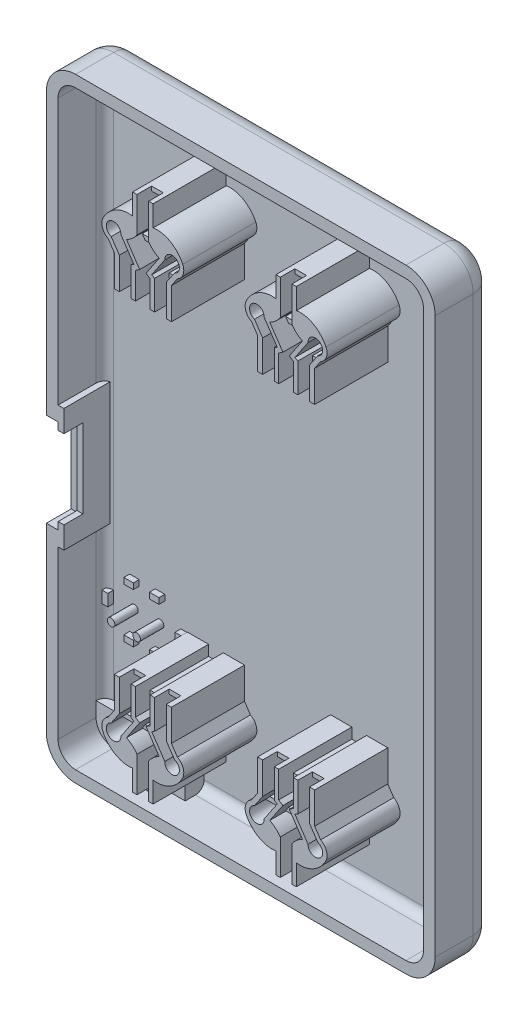
SolidWorks part; units mm, degrees
ref_plane "Alzado" through (0, 0, 0) normal (0, 0, 1) x (1, 0, 0)
ref_plane "Planta" through (0, 0, 0) normal (0, 1, 0) x (1, 0, 0)
ref_plane "Vista lateral" through (0, 0, 0) normal (1, 0, 0) x (0, 0, -1)
sketch "Croquis1" plane through (0, 0, 0) normal (0, 0, 1) x (1, 0, 0)
  line L1 (-97.3166, 96.9231) -> (15.6834, 96.9231)
  line L2 (-107.3166, 86.9231) -> (-107.3166, -103.0769)
  line L3 (-97.3166, -113.0769) -> (15.6834, -113.0769)
  line L4 (25.6834, 86.9231) -> (25.6834, -103.0769)
  arc A0 (15.6834, 96.9231) -> (25.6834, 86.9231) centre (15.6834, 86.9231) cw
  arc A1 (-97.3166, 96.9231) -> (-107.3166, 86.9231) centre (-97.3166, 86.9231) ccw
  arc A2 (15.6834, -113.0769) -> (25.6834, -103.0769) centre (15.6834, -103.0769) ccw
  arc A3 (-107.3166, -103.0769) -> (-97.3166, -113.0769) centre (-97.3166, -103.0769) ccw
  point P6 (25.6834, 96.9231)
  point P9 (-107.3166, 96.9231)
  point P14 (-107.3166, -113.0769)
  dimension "D3" = 10
  dimension "D1" = 210
  dimension "D2" = 133
extrude "Saliente-Extruir1" add sketch "Croquis1" along normal blind 20
fillet "Redondeo1" radius 7 8 edges at (-40.8166, 96.9231, 0) (22.7544, 93.9941, 0) (25.6834, -8.0769, 0) (22.7544, -110.148, 0) (-40.8166, -113.0769, 0) (-104.3877, -110.148, 0) (-107.3166, -8.0769, 0) (-104.3877, 93.9941, 0)
shell "Vaciado1" thickness 4 removed face at (-40.8166, -8.0769, 20)
sketch "Croquis4" plane through (0, 0, 0) normal (0, 0, 1) x (1, 0, 0)
  line L11 (-95.8166, 81.9231) -> (-103.3166, 81.9231)
  line L12 (-97.3166, -109.0769) -> (15.6834, -109.0769) construction
  line L17 (-103.3166, 86.9231) -> (-103.3166, -103.0769) construction
  line L19 (-85.549, -109.0769) -> (-78.3884, -109.0769)
  line L23 (-92.3166, 85.4231) -> (-92.3166, 92.9231)
  line L40 (15.6834, 92.9231) -> (-97.3166, 92.9231) construction
  line L41 (-40.8166, 96.9231) -> (-40.8166, -113.0769)
  line L42 (-85.549, -109.0769) -> (-85.549, -113.0769)
  line L43 (-107.3166, -8.0769) -> (25.6834, -8.0769)
  line L44 (-85.549, -113.0769) -> (-78.3884, -113.0769)
  line L45 (-78.3884, -109.0769) -> (-78.3884, -113.0769)
  line L47 (14.1834, 81.9231) -> (21.6834, 81.9231)
  line L48 (25.6834, -113.0769) -> (-107.3166, -113.0769)
  line L50 (25.6834, -113.0769) -> (25.6834, 96.9231)
  line L51 (25.6834, 96.9231) -> (-107.3166, 96.9231)
  line L52 (-107.3166, -113.0769) -> (-107.3166, 96.9231)
  line L53 (10.6834, 85.4231) -> (10.6834, 92.9231)
  line L54 (-92.3166, -101.5769) -> (-92.3166, -109.0769)
  line L55 (-95.8166, -98.0769) -> (-103.3166, -98.0769)
  line L56 (10.6834, -101.5769) -> (10.6834, -109.0769)
  line L57 (14.1834, -98.0769) -> (21.6834, -98.0769)
  circle A6 centre (-95.8166, 85.4231) radius 3.5
  circle A12 centre (-95.8166, 85.4231) radius 1.6
  circle A14 centre (14.1834, 85.4231) radius 1.6
  circle A15 centre (14.1834, 85.4231) radius 3.5
  circle A17 centre (-95.8166, -101.5769) radius 1.6
  circle A18 centre (-95.8166, -101.5769) radius 3.5
  circle A19 centre (14.1834, -101.5769) radius 1.6
  circle A20 centre (14.1834, -101.5769) radius 3.5
  arc A21 (-103.3166, 81.9231) -> (-92.3166, 92.9231) centre (-95.8166, 85.4231) cw
  arc A22 (10.6834, 92.9231) -> (21.6834, 81.9231) centre (14.1834, 85.4231) cw
  arc A23 (21.6834, -98.0769) -> (10.6834, -109.0769) centre (14.1834, -101.5769) cw
  arc A24 (-103.3166, -98.0769) -> (-92.3166, -109.0769) centre (-95.8166, -101.5769) ccw
extrude "Cortar-Extruir5" cut sketch "Croquis4" along normal through all both and the other way through all from surface contours A17 | A19 | A14 | A12 region at (-95.8166, 85.4231, 0) region at (14.1834, 85.4231, 0) region at (-95.8166, -101.5769, 0) region at (14.1834, -101.5769, 0) starting at face at (-40.8166, -8.0769, 4)
sketch "Croquis5" plane through (0, 0, 0) normal (0, 0, 1) x (1, 0, 0)
  line L8 (-144.4431, 85.9333) -> (-144.4431, 50.2681) construction
  line L150 (-75.9086, 63.6344) -> (-71.0838, 63.6344)
  line L167 (-146.4431, 85.9333) -> (-146.4431, 73.9331)
  line L178 (-146.4431, 73.9331) -> (-142.4431, 73.9331)
  line L185 (-146.4431, 73.9331) -> (-146.4431, 85.9333)
  line L187 (-146.4431, 85.9333) -> (-142.4431, 85.9333)
  line L190 (-146.4431, 85.9333) -> (-147.9431, 85.9333)
  line L196 (-142.4431, 73.9331) -> (-142.4431, 85.9333)
  line L197 (-147.4727, 64.6757) -> (-148.4665, 64.1128)
  line L202 (-152.4665, 64.926) -> (-152.4665, 54.1125)
  line L203 (-148.4665, 54.1125) -> (-152.4665, 54.1125)
  line L204 (-154.2167, 64.8384) -> (-156.2619, 67.8705)
  line L212 (-148.4665, 64.1128) -> (-148.4665, 54.1125)
  line L213 (-151.9463, 71.308) -> (-147.4727, 64.6757)
  line L215 (-152.4665, 54.1125) -> (-154.2167, 54.1125)
  line L216 (-152.4665, 64.926) -> (-155.2624, 69.0712)
  line L217 (-154.2167, 54.1125) -> (-154.2167, 64.8384)
  line L218 (-142.4431, 85.9333) -> (-142.4431, 73.9331)
  line L219 (-145.5428, 64.1681) -> (-146.9665, 63.2078)
  line L221 (-146.9665, 63.2078) -> (-146.9665, 54.1125)
  line L223 (-148.4665, 54.1125) -> (-146.9665, 54.1125)
  line L224 (-150.0254, 70.8139) -> (-145.5428, 64.1681)
  line L225 (-147.9431, 85.9333) -> (-147.9431, 78.778)
  line L226 (-140.4198, 54.1125) -> (-141.9198, 54.1125)
  line L227 (-141.9198, 63.2078) -> (-141.9198, 54.1125)
  line L228 (-143.3435, 64.1681) -> (-141.9198, 63.2078)
  line L229 (-138.8608, 70.8139) -> (-143.3435, 64.1681)
  line L230 (-142.4431, 85.9333) -> (-140.9431, 85.9333)
  line L231 (-140.9431, 85.9333) -> (-140.9431, 78.778)
  line L232 (-134.6696, 64.8384) -> (-132.6244, 67.8705)
  line L233 (-134.6696, 54.1125) -> (-134.6696, 64.8384)
  line L234 (-136.4198, 54.1125) -> (-134.6696, 54.1125)
  line L235 (-136.4198, 64.926) -> (-136.4198, 54.1125)
  line L236 (-136.4198, 64.926) -> (-133.6238, 69.0712)
  line L237 (-136.94, 71.308) -> (-141.4135, 64.6757)
  line L238 (-141.4135, 64.6757) -> (-140.4198, 64.1128)
  line L239 (-140.4198, 64.1128) -> (-140.4198, 54.1125)
  line L241 (-107.3166, 96.9231) -> (-100.3166, 96.9231)
  line L242 (-107.3166, 96.9231) -> (-107.3166, 86.9231)
  line L253 (25.6834, -113.0769) -> (-107.3166, -113.0769)
  line L254 (25.6834, -113.0769) -> (25.6834, 96.9231)
  line L255 (25.6834, 96.9231) -> (-107.3166, 96.9231)
  line L257 (-107.3166, -113.0769) -> (-107.3166, 96.9231)
  line L269 (-18.84, -74.2618) -> (-18.84, -65.1665)
  line L283 (-97.3166, 89.9231) -> (-100.3166, 89.9231)
  line L286 (-100.3166, 89.9231) -> (18.6834, 89.9231)
  line L287 (-100.3166, 89.9231) -> (-100.3166, 39.9231)
  line L288 (-100.3166, 39.9231) -> (18.6834, 39.9231)
  line L289 (18.6834, 89.9231) -> (18.6834, 39.9231)
  line L290 (18.6834, 86.9231) -> (18.6834, -103.0769) construction
  line L292 (-100.3166, 89.9231) -> (-80.3166, 89.9231)
  line L293 (-100.3166, 89.9231) -> (-100.3166, 39.9231)
  line L294 (-100.3166, 39.9231) -> (-80.3166, 39.9231)
  line L295 (-80.3166, 89.9231) -> (-80.3166, 39.9231)
  line L297 (18.6834, 39.9231) -> (-1.3166, 39.9231)
  line L298 (18.6834, 39.9231) -> (18.6834, 89.9231)
  line L299 (18.6834, 89.9231) -> (-1.3166, 89.9231)
  line L300 (-1.3166, 39.9231) -> (-1.3166, 89.9231)
  line L302 (-80.3166, 39.9231) -> (-50.3166, 39.9231)
  line L303 (-80.3166, 39.9231) -> (-80.3166, 89.9231)
  line L304 (-80.3166, 89.9231) -> (-50.3166, 89.9231)
  line L305 (-50.3166, 39.9231) -> (-50.3166, 89.9231)
  line L307 (-1.3166, 39.9231) -> (-31.3166, 39.9231)
  line L308 (-1.3166, 39.9231) -> (-1.3166, 89.9231)
  line L309 (-1.3166, 89.9231) -> (-31.3166, 89.9231)
  line L310 (-31.3166, 39.9231) -> (-31.3166, 89.9231)
  line L313 (-130.4431, 54.1125) -> (-158.4431, 85.9333)
  line L317 (-67.3166, 68.8333) -> (-67.3166, 80.8335)
  line L318 (-72.8198, 66.2081) -> (-68.3462, 59.5758)
  line L319 (-63.3166, 80.8335) -> (-61.8166, 80.8335)
  line L320 (-61.2933, 59.013) -> (-61.2933, 49.0127)
  line L321 (-63.3166, 80.8335) -> (-63.3166, 68.8333)
  line L322 (-70.8989, 65.714) -> (-66.4163, 59.0683)
  line L323 (-59.7343, 65.714) -> (-64.217, 59.0683)
  line L324 (-57.2933, 59.8262) -> (-54.4974, 63.9714)
  line L325 (-75.0902, 59.7386) -> (-77.1354, 62.7707)
  line L326 (-75.0902, 49.0127) -> (-75.0902, 59.7386)
  line L327 (-67.3166, 80.8335) -> (-67.3166, 68.8333)
  line L329 (-61.8166, 80.8335) -> (-61.8166, 73.6781)
  line L330 (-68.3462, 59.5758) -> (-69.34, 59.013)
  line L331 (-66.4163, 59.0683) -> (-67.84, 58.108)
  line L333 (-68.8166, 80.8335) -> (-68.8166, 73.6781)
  line L334 (-55.5431, 49.0127) -> (-55.5431, 59.7386)
  line L335 (-73.34, 49.0127) -> (-75.0902, 49.0127)
  line L336 (-55.5431, 59.7386) -> (-53.4979, 62.7707)
  line L337 (-57.2933, 59.8262) -> (-57.2933, 49.0127)
  line L338 (-67.84, 58.108) -> (-67.84, 49.0127)
  line L339 (-69.34, 49.0127) -> (-67.84, 49.0127)
  line L340 (-57.8135, 66.2081) -> (-62.287, 59.5758)
  line L341 (-63.3166, 68.8333) -> (-63.3166, 80.8335)
  line L342 (-73.34, 59.8262) -> (-73.34, 49.0127)
  line L343 (-61.2933, 49.0127) -> (-62.7933, 49.0127)
  line L345 (-64.217, 59.0683) -> (-62.7933, 58.108)
  line L346 (-62.287, 59.5758) -> (-61.2933, 59.013)
  line L347 (-73.34, 59.8262) -> (-76.1359, 63.9714)
  line L348 (-57.2933, 49.0127) -> (-55.5431, 49.0127)
  line L350 (-62.7933, 58.108) -> (-62.7933, 49.0127)
  line L352 (-67.3166, 80.8335) -> (-68.8166, 80.8335)
  line L353 (-69.34, 59.013) -> (-69.34, 49.0127)
  line L392 (-24.34, -65.1665) -> (-26.0902, -65.1665)
  line L393 (-14.3166, -96.9873) -> (-12.8166, -96.9873)
  line L394 (-20.34, -65.1665) -> (-18.84, -65.1665)
  line L395 (-19.8166, -96.9873) -> (-19.8166, -89.832)
  line L396 (-26.0902, -65.1665) -> (-26.0902, -75.8924)
  line L397 (-13.287, -75.7297) -> (-12.2933, -75.1668)
  line L398 (-13.7933, -74.2618) -> (-13.7933, -65.1665)
  line L399 (-26.0902, -75.8924) -> (-28.1354, -78.9245)
  line L400 (-12.8166, -96.9873) -> (-12.8166, -89.832)
  line L401 (-6.5431, -75.8924) -> (-4.4979, -78.9245)
  line L402 (-12.2933, -65.1665) -> (-13.7933, -65.1665)
  line L403 (-20.34, -75.1668) -> (-20.34, -65.1665)
  line L404 (-21.8989, -81.8679) -> (-17.4163, -75.2221)
  line L405 (-10.7343, -81.8679) -> (-15.217, -75.2221)
  line L406 (-24.34, -75.98) -> (-27.1359, -80.1252)
  line L407 (-15.217, -75.2221) -> (-13.7933, -74.2618)
  line L408 (-17.4163, -75.2221) -> (-18.84, -74.2618)
  line L409 (-19.3462, -75.7297) -> (-20.34, -75.1668)
  line L410 (-8.2933, -75.98) -> (-8.2933, -65.1665)
  line L411 (-14.3166, -96.9873) -> (-14.3166, -84.9871)
  line L412 (-14.3166, -84.9871) -> (-14.3166, -96.9873)
  line L413 (-24.34, -75.98) -> (-24.34, -65.1665)
  line L414 (-12.2933, -75.1668) -> (-12.2933, -65.1665)
  line L415 (-8.2933, -65.1665) -> (-6.5431, -65.1665)
  line L416 (-8.8135, -82.362) -> (-13.287, -75.7297)
  line L417 (-18.3166, -96.9873) -> (-18.3166, -84.9871)
  line L418 (-6.5431, -65.1665) -> (-6.5431, -75.8924)
  line L419 (-23.8198, -82.362) -> (-19.3462, -75.7297)
  line L420 (-8.2933, -75.98) -> (-5.4974, -80.1252)
  line L421 (-18.3166, -96.9873) -> (-19.8166, -96.9873)
  line L422 (-18.3166, -84.9871) -> (-18.3166, -96.9873)
  line L423 (-69.34, -75.1668) -> (-69.34, -65.1665)
  line L424 (-67.3166, -96.9873) -> (-68.8166, -96.9873)
  line L425 (-62.7933, -74.2618) -> (-62.7933, -65.1665)
  line L426 (-57.2933, -65.1665) -> (-55.5431, -65.1665)
  line L427 (-73.34, -75.98) -> (-76.1359, -80.1252)
  line L428 (-62.287, -75.7297) -> (-61.2933, -75.1668)
  line L429 (-64.217, -75.2221) -> (-62.7933, -74.2618)
  line L430 (-61.2933, -65.1665) -> (-62.7933, -65.1665)
  line L431 (-73.34, -75.98) -> (-73.34, -65.1665)
  line L432 (-63.3166, -84.9871) -> (-63.3166, -96.9873)
  line L433 (-57.8135, -82.362) -> (-62.287, -75.7297)
  line L434 (-69.34, -65.1665) -> (-67.84, -65.1665)
  line L435 (-67.84, -74.2618) -> (-67.84, -65.1665)
  line L436 (-57.2933, -75.98) -> (-57.2933, -65.1665)
  line L437 (-55.5431, -75.8924) -> (-53.4979, -78.9245)
  line L438 (-73.34, -65.1665) -> (-75.0902, -65.1665)
  line L439 (-55.5431, -65.1665) -> (-55.5431, -75.8924)
  line L440 (-68.8166, -96.9873) -> (-68.8166, -89.832)
  line L441 (-66.4163, -75.2221) -> (-67.84, -74.2618)
  line L442 (-68.3462, -75.7297) -> (-69.34, -75.1668)
  line L443 (-61.8166, -96.9873) -> (-61.8166, -89.832)
  line L444 (-67.3166, -96.9873) -> (-67.3166, -84.9871)
  line L445 (-75.0902, -65.1665) -> (-75.0902, -75.8924)
  line L446 (-75.0902, -75.8924) -> (-77.1354, -78.9245)
  line L447 (-57.2933, -75.98) -> (-54.4974, -80.1252)
  line L448 (-59.7343, -81.8679) -> (-64.217, -75.2221)
  line L449 (-70.8989, -81.8679) -> (-66.4163, -75.2221)
  line L450 (-63.3166, -96.9873) -> (-63.3166, -84.9871)
  line L451 (-61.2933, -75.1668) -> (-61.2933, -65.1665)
  line L452 (-63.3166, -96.9873) -> (-61.8166, -96.9873)
  line L453 (-72.8198, -82.362) -> (-68.3462, -75.7297)
  line L454 (-67.3166, -84.9871) -> (-67.3166, -96.9873)
  line L457 (-73.34, 49.0127) -> (-69.34, 49.0127)
  line L458 (-73.34, 49.0127) -> (-73.34, 50.515)
  line L459 (-73.34, 50.515) -> (-69.34, 50.515)
  line L460 (-69.34, 49.0127) -> (-69.34, 50.515)
  line L461 (-61.2933, 49.0127) -> (-57.2933, 49.0127)
  line L462 (-61.2933, 49.0127) -> (-61.2933, 50.515)
  line L463 (-61.2933, 50.515) -> (-57.2933, 50.515)
  line L464 (-57.2933, 49.0127) -> (-57.2933, 50.515)
  line L465 (-61.2933, 58.108) -> (-57.2933, 58.108)
  line L466 (-61.2933, 58.108) -> (-61.2933, 56.6032)
  line L467 (-61.2933, 56.6032) -> (-57.2933, 56.6032)
  line L468 (-57.2933, 58.108) -> (-57.2933, 56.6032)
  line L469 (-69.34, 56.6032) -> (-73.34, 56.6032)
  line L470 (-69.34, 56.6032) -> (-69.34, 58.108)
  line L471 (-69.34, 58.108) -> (-73.34, 58.108)
  line L472 (-73.34, 56.6032) -> (-73.34, 58.108)
  line L476 (-71.0838, 63.6344) -> (-72.0951, 65.1338)
  line L477 (-72.0951, 65.1338) -> (-77.5101, 65.1338)
  line L478 (-70.5075, 65.1338) -> (-60.1257, 65.1338)
  line L480 (-58.5382, 65.1338) -> (-53.1232, 65.1338)
  line L482 (-69.4962, 63.6344) -> (-61.1371, 63.6344)
  line L484 (-59.5495, 63.6344) -> (-54.7246, 63.6344)
  line L487 (-67.3166, 80.8335) -> (-63.3166, 80.8335)
  line L488 (-67.3166, 80.8335) -> (-67.3166, 79.3376)
  line L489 (-67.3166, 79.3376) -> (-63.3166, 79.3376)
  line L490 (-63.3166, 80.8335) -> (-63.3166, 79.3376)
  line L495 (-67.84, 54.1125) -> (-62.7933, 54.1125)
  line L496 (-67.84, 54.1125) -> (-67.84, 52.6136)
  line L497 (-67.84, 52.6136) -> (-62.7933, 52.6136)
  line L498 (-62.7933, 54.1125) -> (-62.7933, 52.6136)
  line L499 (-18.84, 54.1125) -> (-18.84, 52.6136)
  line L500 (-13.7933, 52.6136) -> (-18.84, 52.6136)
  line L501 (-13.7933, 54.1125) -> (-13.7933, 52.6136)
  line L502 (-13.7933, 54.1125) -> (-18.84, 54.1125)
  line L503 (-18.3166, 80.8335) -> (-18.3166, 79.3376)
  line L504 (-14.3166, 79.3376) -> (-18.3166, 79.3376)
  line L505 (-14.3166, 80.8335) -> (-14.3166, 79.3376)
  line L506 (-14.3166, 80.8335) -> (-18.3166, 80.8335)
  line L507 (-22.0838, 63.6344) -> (-26.9086, 63.6344)
  line L508 (-12.1371, 63.6344) -> (-20.4962, 63.6344)
  line L509 (-23.0951, 65.1338) -> (-28.5101, 65.1338)
  line L510 (-11.1257, 65.1338) -> (-21.5075, 65.1338)
  line L511 (-9.5382, 65.1338) -> (-4.1232, 65.1338)
  line L512 (-10.5495, 63.6344) -> (-9.5382, 65.1338)
  line L513 (-8.2933, 56.6032) -> (-8.2933, 58.108)
  line L514 (-12.2933, 58.108) -> (-8.2933, 58.108)
  line L515 (-12.2933, 56.6032) -> (-12.2933, 58.108)
  line L516 (-12.2933, 56.6032) -> (-8.2933, 56.6032)
  line L517 (-24.34, 58.108) -> (-24.34, 56.6032)
  line L518 (-20.34, 56.6032) -> (-24.34, 56.6032)
  line L519 (-20.34, 58.108) -> (-20.34, 56.6032)
  line L520 (-20.34, 58.108) -> (-24.34, 58.108)
  line L521 (-24.34, 49.0127) -> (-24.34, 50.515)
  line L522 (-20.34, 50.515) -> (-24.34, 50.515)
  line L523 (-20.34, 49.0127) -> (-20.34, 50.515)
  line L524 (-20.34, 49.0127) -> (-24.34, 49.0127)
  line L525 (-12.2933, 49.0127) -> (-12.2933, 50.515)
  line L526 (-8.2933, 50.515) -> (-12.2933, 50.515)
  line L527 (-8.2933, 49.0127) -> (-8.2933, 50.515)
  line L528 (-8.2933, 49.0127) -> (-12.2933, 49.0127)
  line L529 (-12.2933, 59.013) -> (-12.2933, 49.0127)
  line L530 (-14.3166, 80.8335) -> (-12.8166, 80.8335)
  line L531 (-18.84, 58.108) -> (-18.84, 49.0127)
  line L532 (-24.34, 49.0127) -> (-26.0902, 49.0127)
  line L533 (-8.2933, 59.8262) -> (-5.4974, 63.9714)
  line L534 (-19.3462, 59.5758) -> (-20.34, 59.013)
  line L535 (-17.4163, 59.0683) -> (-18.84, 58.108)
  line L536 (-20.34, 49.0127) -> (-18.84, 49.0127)
  line L537 (-8.2933, 59.8262) -> (-8.2933, 49.0127)
  line L538 (-18.3166, 68.8333) -> (-18.3166, 80.8335)
  line L539 (-23.8198, 66.2081) -> (-19.3462, 59.5758)
  line L540 (-12.2933, 49.0127) -> (-13.7933, 49.0127)
  line L541 (-13.7933, 58.108) -> (-13.7933, 49.0127)
  line L542 (-24.34, 59.8262) -> (-24.34, 49.0127)
  line L543 (-26.0902, 59.7386) -> (-28.1354, 62.7707)
  line L544 (-8.2933, 49.0127) -> (-6.5431, 49.0127)
  line L545 (-26.0902, 49.0127) -> (-26.0902, 59.7386)
  line L546 (-12.8166, 80.8335) -> (-12.8166, 73.6781)
  line L547 (-15.217, 59.0683) -> (-13.7933, 58.108)
  line L548 (-13.287, 59.5758) -> (-12.2933, 59.013)
  line L549 (-19.8166, 80.8335) -> (-19.8166, 73.6781)
  line L550 (-14.3166, 80.8335) -> (-14.3166, 68.8333)
  line L551 (-6.5431, 49.0127) -> (-6.5431, 59.7386)
  line L552 (-6.5431, 59.7386) -> (-4.4979, 62.7707)
  line L553 (-24.34, 59.8262) -> (-27.1359, 63.9714)
  line L554 (-21.8989, 65.714) -> (-17.4163, 59.0683)
  line L555 (-10.7343, 65.714) -> (-15.217, 59.0683)
  line L556 (-18.3166, 80.8335) -> (-18.3166, 68.8333)
  line L557 (-20.34, 59.013) -> (-20.34, 49.0127)
  line L558 (-18.3166, 80.8335) -> (-19.8166, 80.8335)
  line L559 (-8.8135, 66.2081) -> (-13.287, 59.5758)
  line L560 (-14.3166, 68.8333) -> (-14.3166, 80.8335)
  line L561 (-5.7246, 63.6344) -> (-10.5495, 63.6344)
  line L562 (-100.3166, -8.0769) -> (18.6834, -8.0769)
  line L563 (-100.3166, -103.0769) -> (-100.3166, 86.9231) construction
  line L564 (-5.7246, -79.7882) -> (-10.5495, -79.7882)
  line L565 (-14.3166, -84.9871) -> (-14.3166, -96.9873)
  line L566 (-8.8135, -82.362) -> (-13.287, -75.7297)
  line L567 (-18.3166, -96.9873) -> (-19.8166, -96.9873)
  line L568 (-20.34, -75.1668) -> (-20.34, -65.1665)
  line L569 (-18.3166, -96.9873) -> (-18.3166, -84.9871)
  line L570 (-10.7343, -81.8679) -> (-15.217, -75.2221)
  line L571 (-21.8989, -81.8679) -> (-17.4163, -75.2221)
  line L572 (-24.34, -75.98) -> (-27.1359, -80.1252)
  line L573 (-6.5431, -75.8924) -> (-4.4979, -78.9245)
  line L574 (-6.5431, -65.1665) -> (-6.5431, -75.8924)
  line L575 (-14.3166, -96.9873) -> (-14.3166, -84.9871)
  line L576 (-19.8166, -96.9873) -> (-19.8166, -89.832)
  line L577 (-13.287, -75.7297) -> (-12.2933, -75.1668)
  line L578 (-15.217, -75.2221) -> (-13.7933, -74.2618)
  line L579 (-12.8166, -96.9873) -> (-12.8166, -89.832)
  line L580 (-26.0902, -65.1665) -> (-26.0902, -75.8924)
  line L581 (-8.2933, -65.1665) -> (-6.5431, -65.1665)
  line L582 (-26.0902, -75.8924) -> (-28.1354, -78.9245)
  line L583 (-24.34, -75.98) -> (-24.34, -65.1665)
  line L584 (-13.7933, -74.2618) -> (-13.7933, -65.1665)
  line L585 (-12.2933, -65.1665) -> (-13.7933, -65.1665)
  line L586 (-23.8198, -82.362) -> (-19.3462, -75.7297)
  line L587 (-18.3166, -84.9871) -> (-18.3166, -96.9873)
  line L588 (-8.2933, -75.98) -> (-8.2933, -65.1665)
  line L589 (-20.34, -65.1665) -> (-18.84, -65.1665)
  line L590 (-17.4163, -75.2221) -> (-18.84, -74.2618)
  line L591 (-19.3462, -75.7297) -> (-20.34, -75.1668)
  line L592 (-8.2933, -75.98) -> (-5.4974, -80.1252)
  line L593 (-24.34, -65.1665) -> (-26.0902, -65.1665)
  line L594 (-18.84, -74.2618) -> (-18.84, -65.1665)
  line L595 (-14.3166, -96.9873) -> (-12.8166, -96.9873)
  line L596 (-12.2933, -75.1668) -> (-12.2933, -65.1665)
  line L597 (-8.2933, -65.1665) -> (-12.2933, -65.1665)
  line L598 (-8.2933, -65.1665) -> (-8.2933, -66.6689)
  line L599 (-8.2933, -66.6689) -> (-12.2933, -66.6689)
  line L600 (-12.2933, -65.1665) -> (-12.2933, -66.6689)
  line L601 (-20.34, -65.1665) -> (-24.34, -65.1665)
  line L602 (-20.34, -65.1665) -> (-20.34, -66.6689)
  line L603 (-20.34, -66.6689) -> (-24.34, -66.6689)
  line L604 (-24.34, -65.1665) -> (-24.34, -66.6689)
  line L605 (-20.34, -74.2618) -> (-24.34, -74.2618)
  line L606 (-20.34, -74.2618) -> (-20.34, -72.757)
  line L607 (-20.34, -72.757) -> (-24.34, -72.757)
  line L608 (-24.34, -74.2618) -> (-24.34, -72.757)
  line L609 (-12.2933, -72.757) -> (-8.2933, -72.757)
  line L610 (-12.2933, -72.757) -> (-12.2933, -74.2618)
  line L611 (-12.2933, -74.2618) -> (-8.2933, -74.2618)
  line L612 (-8.2933, -72.757) -> (-8.2933, -74.2618)
  line L613 (-10.5495, -79.7882) -> (-9.5382, -81.2876)
  line L614 (-9.5382, -81.2876) -> (-4.1232, -81.2876)
  line L615 (-11.1257, -81.2876) -> (-21.5075, -81.2876)
  line L616 (-23.0951, -81.2876) -> (-28.5101, -81.2876)
  line L617 (-12.1371, -79.7882) -> (-20.4962, -79.7882)
  line L618 (-22.0838, -79.7882) -> (-26.9086, -79.7882)
  line L619 (-14.3166, -96.9873) -> (-18.3166, -96.9873)
  line L620 (-14.3166, -96.9873) -> (-14.3166, -95.4915)
  line L621 (-14.3166, -95.4915) -> (-18.3166, -95.4915)
  line L622 (-18.3166, -96.9873) -> (-18.3166, -95.4915)
  line L623 (-13.7933, -70.2663) -> (-18.84, -70.2663)
  line L624 (-13.7933, -70.2663) -> (-13.7933, -68.7675)
  line L625 (-13.7933, -68.7675) -> (-18.84, -68.7675)
  line L626 (-18.84, -70.2663) -> (-18.84, -68.7675)
  line L627 (-62.7933, -70.2663) -> (-62.7933, -68.7675)
  line L628 (-67.84, -68.7675) -> (-62.7933, -68.7675)
  line L629 (-67.84, -70.2663) -> (-67.84, -68.7675)
  line L630 (-67.84, -70.2663) -> (-62.7933, -70.2663)
  line L631 (-63.3166, -96.9873) -> (-63.3166, -95.4915)
  line L632 (-67.3166, -95.4915) -> (-63.3166, -95.4915)
  line L633 (-67.3166, -96.9873) -> (-67.3166, -95.4915)
  line L634 (-67.3166, -96.9873) -> (-63.3166, -96.9873)
  line L635 (-59.5495, -79.7882) -> (-54.7246, -79.7882)
  line L636 (-69.4962, -79.7882) -> (-61.1371, -79.7882)
  line L637 (-58.5382, -81.2876) -> (-53.1232, -81.2876)
  line L638 (-70.5075, -81.2876) -> (-60.1257, -81.2876)
  line L639 (-72.0951, -81.2876) -> (-77.5101, -81.2876)
  line L640 (-71.0838, -79.7882) -> (-72.0951, -81.2876)
  line L641 (-73.34, -72.757) -> (-73.34, -74.2618)
  line L642 (-69.34, -74.2618) -> (-73.34, -74.2618)
  line L643 (-69.34, -72.757) -> (-69.34, -74.2618)
  line L644 (-69.34, -72.757) -> (-73.34, -72.757)
  line L645 (-57.2933, -74.2618) -> (-57.2933, -72.757)
  line L646 (-61.2933, -72.757) -> (-57.2933, -72.757)
  line L647 (-61.2933, -74.2618) -> (-61.2933, -72.757)
  line L648 (-61.2933, -74.2618) -> (-57.2933, -74.2618)
  line L649 (-57.2933, -65.1665) -> (-57.2933, -66.6689)
  line L650 (-61.2933, -66.6689) -> (-57.2933, -66.6689)
  line L651 (-61.2933, -65.1665) -> (-61.2933, -66.6689)
  line L652 (-61.2933, -65.1665) -> (-57.2933, -65.1665)
  line L653 (-69.34, -65.1665) -> (-69.34, -66.6689)
  line L654 (-73.34, -66.6689) -> (-69.34, -66.6689)
  line L655 (-73.34, -65.1665) -> (-73.34, -66.6689)
  line L656 (-73.34, -65.1665) -> (-69.34, -65.1665)
  line L657 (-69.34, -75.1668) -> (-69.34, -65.1665)
  line L658 (-67.3166, -96.9873) -> (-68.8166, -96.9873)
  line L659 (-62.7933, -74.2618) -> (-62.7933, -65.1665)
  line L660 (-57.2933, -65.1665) -> (-55.5431, -65.1665)
  line L661 (-73.34, -75.98) -> (-76.1359, -80.1252)
  line L662 (-62.287, -75.7297) -> (-61.2933, -75.1668)
  line L663 (-64.217, -75.2221) -> (-62.7933, -74.2618)
  line L664 (-61.2933, -65.1665) -> (-62.7933, -65.1665)
  line L665 (-73.34, -75.98) -> (-73.34, -65.1665)
  line L666 (-63.3166, -84.9871) -> (-63.3166, -96.9873)
  line L667 (-57.8135, -82.362) -> (-62.287, -75.7297)
  line L668 (-69.34, -65.1665) -> (-67.84, -65.1665)
  line L669 (-67.84, -74.2618) -> (-67.84, -65.1665)
  line L670 (-57.2933, -75.98) -> (-57.2933, -65.1665)
  line L671 (-55.5431, -75.8924) -> (-53.4979, -78.9245)
  line L672 (-73.34, -65.1665) -> (-75.0902, -65.1665)
  line L673 (-55.5431, -65.1665) -> (-55.5431, -75.8924)
  line L674 (-68.8166, -96.9873) -> (-68.8166, -89.832)
  line L675 (-66.4163, -75.2221) -> (-67.84, -74.2618)
  line L676 (-68.3462, -75.7297) -> (-69.34, -75.1668)
  line L677 (-61.8166, -96.9873) -> (-61.8166, -89.832)
  line L678 (-67.3166, -96.9873) -> (-67.3166, -84.9871)
  line L679 (-75.0902, -65.1665) -> (-75.0902, -75.8924)
  line L680 (-75.0902, -75.8924) -> (-77.1354, -78.9245)
  line L681 (-57.2933, -75.98) -> (-54.4974, -80.1252)
  line L682 (-59.7343, -81.8679) -> (-64.217, -75.2221)
  line L683 (-70.8989, -81.8679) -> (-66.4163, -75.2221)
  line L684 (-63.3166, -96.9873) -> (-63.3166, -84.9871)
  line L685 (-61.2933, -75.1668) -> (-61.2933, -65.1665)
  line L686 (-63.3166, -96.9873) -> (-61.8166, -96.9873)
  line L687 (-72.8198, -82.362) -> (-68.3462, -75.7297)
  line L688 (-67.3166, -84.9871) -> (-67.3166, -96.9873)
  line L689 (-75.9086, -79.7882) -> (-71.0838, -79.7882)
  line L690 (-97.3166, -109.0769) -> (15.6834, -109.0769) construction
  line L691 (-81.8788, -113.0769) -> (-74.9415, -113.0769)
  line L692 (-81.8788, -113.0769) -> (-81.8788, -109.0769)
  line L693 (-81.8788, -109.0769) -> (-74.9415, -109.0769)
  line L694 (-74.9415, -113.0769) -> (-74.9415, -109.0769)
  line L695 (-87.3438, -109.0769) -> (-81.8788, -109.0769)
  line L697 (-84.8438, -103.0769) -> (-71.844, -103.0769)
  line L698 (-87.3438, -103.0769) -> (-87.3438, -109.0769)
  line L699 (-84.8438, -100.5769) -> (-71.844, -100.5769)
  line L700 (-69.344, -103.0769) -> (-69.344, -109.0769)
  line L701 (-97.3166, -109.0769) -> (15.6834, -109.0769) construction
  line L702 (-74.9415, -109.0769) -> (-69.344, -109.0769)
  line L704 (-78.4102, -109.0769) -> (-78.4102, -113.0769)
  line L705 (-100.3166, -74.8411) -> (-77.3166, -74.8411)
  line L706 (-100.3166, -74.8411) -> (-100.3166, -59.8411)
  line L707 (-100.3166, -59.8411) -> (-77.3166, -59.8411)
  line L708 (-77.3166, -74.8411) -> (-77.3166, -59.8411)
  line L709 (-77.3166, -74.8411) -> (-82.8166, -74.8411)
  line L710 (-77.3166, -74.8411) -> (-77.3166, -59.8411)
  line L711 (-77.3166, -59.8411) -> (-82.8166, -59.8411)
  line L713 (-94.8166, -59.8411) -> (-91.5666, -59.8411)
  line L714 (-91.5666, -59.8411) -> (-86.0666, -59.8411)
  line L716 (-91.5666, -74.8411) -> (-86.0666, -74.8411)
  line L718 (-94.8166, -59.8411) -> (-94.8166, -74.8411)
  line L719 (-94.8166, -74.8411) -> (-91.5666, -74.8411)
  line L720 (-91.5666, -59.8411) -> (-91.5666, -74.8411)
  line L722 (-100.3166, -59.8411) -> (-94.8166, -59.8411)
  line L723 (-100.3166, -59.8411) -> (-100.3166, -74.8411)
  line L724 (-100.3166, -74.8411) -> (-94.8166, -74.8411)
  line L726 (-86.0666, -59.8411) -> (-82.8166, -59.8411)
  line L727 (-86.0666, -59.8411) -> (-86.0666, -74.8411)
  line L728 (-86.0666, -74.8411) -> (-82.8166, -74.8411)
  line L729 (-82.8166, -59.8411) -> (-82.8166, -74.8411)
  line L730 (-100.3166, -59.8411) -> (-77.3166, -59.8411)
  line L734 (-77.3166, -74.8411) -> (-100.3166, -74.8411)
  line L738 (-100.3166, -67.3411) -> (-101.3166, -67.3411)
  line L739 (18.6834, 86.9231) -> (18.6834, -103.0769) construction
  line L740 (-102.3166, -65.3411) -> (-100.3166, -65.3411)
  line L741 (-102.3166, -65.3411) -> (-102.3166, -69.3411)
  line L742 (-102.3166, -69.3411) -> (-100.3166, -69.3411)
  line L743 (-100.3166, -65.3411) -> (-100.3166, -69.3411)
  line L744 (-102.3166, -65.3411) -> (-100.3166, -69.3411) construction
  line L745 (-102.3166, -69.3411) -> (-100.3166, -65.3411) construction
  line L746 (-100.3166, -69.3411) -> (-77.3166, -69.3411)
  line L747 (18.6834, -47.5353) -> (-62.7933, -47.5353)
  line L750 (-77.3166, -65.3411) -> (-75.0902, -65.3411)
  line L751 (-77.3166, -69.3411) -> (-77.3166, -65.3411)
  line L754 (-77.3166, -65.3411) -> (-77.3166, -69.3411)
  line L755 (-77.3166, -69.3411) -> (-75.0902, -69.3411)
  line L756 (-75.0902, -65.3411) -> (-75.0902, -69.3411)
  line L757 (-94.8166, -74.8411) -> (-91.5666, -74.8411)
  line L758 (-94.8166, -74.8411) -> (-94.8166, -76.8411)
  line L759 (-94.8166, -76.8411) -> (-91.5666, -76.8411)
  line L760 (-91.5666, -74.8411) -> (-91.5666, -76.8411)
  line L761 (-86.0666, -74.8411) -> (-82.8166, -74.8411)
  line L762 (-86.0666, -74.8411) -> (-86.0666, -76.8411)
  line L763 (-86.0666, -76.8411) -> (-82.8166, -76.8411)
  line L764 (-82.8166, -74.8411) -> (-82.8166, -76.8411)
  line L765 (-94.8166, -59.8411) -> (-91.5666, -59.8411)
  line L766 (-94.8166, -59.8411) -> (-94.8166, -57.8411)
  line L767 (-94.8166, -57.8411) -> (-91.5666, -57.8411)
  line L768 (-91.5666, -59.8411) -> (-91.5666, -57.8411)
  line L769 (-86.0666, -59.8411) -> (-82.8166, -59.8411)
  line L770 (-86.0666, -59.8411) -> (-86.0666, -57.8411)
  line L771 (-86.0666, -57.8411) -> (-82.8166, -57.8411)
  line L772 (-82.8166, -59.8411) -> (-82.8166, -57.8411)
  line L773 (18.6834, -47.5353) -> (18.6834, 32.988)
  line L774 (18.6834, 32.988) -> (-62.7933, 32.988)
  line L775 (-62.7933, -47.5353) -> (-62.7933, 32.988)
  line L776 (-103.3166, 86.9231) -> (-103.3166, -103.0769) construction
  line L777 (-107.3166, -41.0434) -> (-77.3166, -41.0434)
  line L778 (-107.3166, -41.0434) -> (-107.3166, -9.0434)
  line L779 (-107.3166, -9.0434) -> (-77.3166, -9.0434)
  line L780 (-77.3166, -41.0434) -> (-77.3166, -9.0434)
  line L781 (-77.3166, -41.0434) -> (-87.3166, -41.0434)
  line L782 (-77.3166, -41.0434) -> (-77.3166, -9.0434)
  line L783 (-77.3166, -9.0434) -> (-87.3166, -9.0434)
  line L784 (-87.3166, -41.0434) -> (-87.3166, -9.0434)
  line L785 (-107.3166, -9.0434) -> (-87.3166, -9.0434)
  line L786 (-107.3166, -9.0434) -> (-107.3166, -13.0467)
  line L787 (-107.3166, -13.0467) -> (-87.3166, -13.0467)
  line L788 (-87.3166, -9.0434) -> (-87.3166, -13.0467)
  line L789 (-87.3166, -13.0467) -> (-77.3166, -13.0467)
  line L790 (-87.3166, -13.0467) -> (-87.3166, -27.5467)
  line L791 (-87.3166, -27.5467) -> (-77.3166, -27.5467)
  line L792 (-77.3166, -13.0467) -> (-77.3166, -27.5467)
  line L793 (-87.3166, -41.0434) -> (-105.3166, -41.0434)
  line L794 (-87.3166, -41.0434) -> (-87.3166, -9.0434)
  line L795 (-87.3166, -9.0434) -> (-105.3166, -9.0434)
  line L796 (-105.3166, -41.0434) -> (-105.3166, -9.0434)
  line L797 (-105.3166, -9.0434) -> (-103.3166, -9.0434)
  line L798 (-105.3166, -9.0434) -> (-105.3166, -41.0434)
  line L799 (-105.3166, -41.0434) -> (-103.3166, -41.0434)
  line L800 (-103.3166, -9.0434) -> (-103.3166, -41.0434)
  line L802 (-103.3166, -9.0434) -> (-101.3166, -9.0434)
  line L803 (-103.3166, -9.0434) -> (-103.3166, -11.5434)
  line L804 (-103.3166, -11.5434) -> (-101.3166, -11.5434)
  line L805 (-101.3166, -9.0434) -> (-101.3166, -11.5434)
  line L806 (-103.3166, -41.0434) -> (-101.3166, -41.0434)
  line L807 (-103.3166, -41.0434) -> (-103.3166, -38.5434)
  line L808 (-103.3166, -38.5434) -> (-101.3166, -38.5434)
  line L809 (-101.3166, -41.0434) -> (-101.3166, -38.5434)
  line L810 (-101.3166, -9.0434) -> (-103.3166, -9.0434)
  line L811 (-101.3166, -9.0434) -> (-101.3166, -4.0434)
  line L812 (-101.3166, -4.0434) -> (-103.3166, -4.0434)
  line L813 (-103.3166, -9.0434) -> (-103.3166, -4.0434)
  line L814 (-101.3166, -41.0434) -> (-103.3166, -41.0434)
  line L815 (-101.3166, -41.0434) -> (-101.3166, -46.0434)
  line L816 (-101.3166, -46.0434) -> (-103.3166, -46.0434)
  line L817 (-103.3166, -41.0434) -> (-103.3166, -46.0434)
  line L818 (-101.3166, -11.5434) -> (-103.3166, -11.5434)
  line L819 (-101.3166, -11.5434) -> (-101.3166, -38.5434)
  line L820 (-101.3166, -38.5434) -> (-103.3166, -38.5434)
  line L821 (-103.3166, -11.5434) -> (-103.3166, -38.5434)
  arc A19 (-151.9463, 71.308) -> (-155.2624, 69.0712) centre (-154.4431, 71.4331) ccw
  arc A20 (-158.0871, 73.0829) -> (-156.2619, 67.8705) centre (-154.4431, 71.4331) ccw
  arc A22 (-130.7992, 73.0829) -> (-132.6244, 67.8705) centre (-134.4431, 71.4331) cw
  arc A25 (-51.6727, 67.9831) -> (-53.4979, 62.7707) centre (-55.3166, 66.3333) cw
  arc A26 (-57.8135, 66.2081) -> (-54.4974, 63.9714) centre (-55.3166, 66.3333) cw
  arc A27 (-136.94, 71.308) -> (-133.6238, 69.0712) centre (-134.4431, 71.4331) cw
  arc A28 (-72.8198, 66.2081) -> (-76.1359, 63.9714) centre (-75.3166, 66.3333) ccw
  arc A29 (-78.9606, 67.9831) -> (-77.1354, 62.7707) centre (-75.3166, 66.3333) ccw
  arc A31 (-2.6727, 67.9831) -> (-4.4979, 62.7707) centre (-6.3166, 66.3333) cw
  arc A32 (-8.8135, 66.2081) -> (-5.4974, 63.9714) centre (-6.3166, 66.3333) cw
  arc A34 (-29.9606, -84.1369) -> (-28.1354, -78.9245) centre (-26.3166, -82.4871) cw
  arc A35 (-2.6727, -84.1369) -> (-4.4979, -78.9245) centre (-6.3166, -82.4871) ccw
  arc A36 (-8.8135, -82.362) -> (-5.4974, -80.1252) centre (-6.3166, -82.4871) ccw
  arc A37 (-23.8198, -82.362) -> (-27.1359, -80.1252) centre (-26.3166, -82.4871) cw
  arc A38 (-78.9606, -84.1369) -> (-77.1354, -78.9245) centre (-75.3166, -82.4871) cw
  arc A39 (-72.8198, -82.362) -> (-76.1359, -80.1252) centre (-75.3166, -82.4871) cw
  arc A40 (-57.8135, -82.362) -> (-54.4974, -80.1252) centre (-55.3166, -82.4871) ccw
  arc A41 (-51.6727, -84.1369) -> (-53.4979, -78.9245) centre (-55.3166, -82.4871) ccw
  arc A42 (-23.8198, 66.2081) -> (-27.1359, 63.9714) centre (-26.3166, 66.3333) ccw
  arc A43 (-29.9606, 67.9831) -> (-28.1354, 62.7707) centre (-26.3166, 66.3333) ccw
  arc A44 (-29.9606, -84.1369) -> (-28.1354, -78.9245) centre (-26.3166, -82.4871) cw
  arc A45 (-23.8198, -82.362) -> (-27.1359, -80.1252) centre (-26.3166, -82.4871) cw
  arc A46 (-8.8135, -82.362) -> (-5.4974, -80.1252) centre (-6.3166, -82.4871) ccw
  arc A47 (-2.6727, -84.1369) -> (-4.4979, -78.9245) centre (-6.3166, -82.4871) ccw
  arc A48 (-78.9606, -84.1369) -> (-77.1354, -78.9245) centre (-75.3166, -82.4871) cw
  arc A49 (-72.8198, -82.362) -> (-76.1359, -80.1252) centre (-75.3166, -82.4871) cw
  arc A50 (-57.8135, -82.362) -> (-54.4974, -80.1252) centre (-55.3166, -82.4871) ccw
  arc A51 (-51.6727, -84.1369) -> (-53.4979, -78.9245) centre (-55.3166, -82.4871) ccw
  circle A52 centre (-84.8438, -103.0769) radius 2.5
  circle A53 centre (-71.844, -103.0769) radius 2.5
  circle A54 centre (-84.8438, -103.0769) radius 1.25
  circle A55 centre (-71.844, -103.0769) radius 1.25
  circle A56 centre (-84.4416, -67.352) radius 1.3
  circle A57 centre (-93.1916, -67.3411) radius 1.3
  spline S0 degree 2 poles (-146.4431, 73.9331) (-147.8203, 71.9193) (-150.0254, 70.8139) knots 0 0 0 1 1 1
  spline S1 degree 3 poles (-147.9431, 78.778) (-152.1151, 79.5461) (-156.3509, 76.7762) (-158.0871, 73.0829) knots 0 0 0 0 1 1 1 1
  spline S2 degree 2 poles (-142.4431, 73.9331) (-141.066, 71.9193) (-138.8608, 70.8139) knots 0 0 0 1 1 1
  spline S3 degree 3 poles (-140.9431, 78.778) (-136.7712, 79.5461) (-132.5354, 76.7762) (-130.7992, 73.0829) knots 0 0 0 0 1 1 1 1
  spline S4 degree 3 poles (-61.8166, 73.6781) (-57.6447, 74.4463) (-53.4089, 71.6763) (-51.6727, 67.9831) knots 0 0 0 0 1 1 1 1
  spline S5 degree 3 poles (-68.8166, 73.6781) (-72.9886, 74.4463) (-77.2244, 71.6763) (-78.9606, 67.9831) knots 0 0 0 0 1 1 1 1
  spline S6 degree 2 poles (-67.3166, 68.8333) (-68.6938, 66.8195) (-70.8989, 65.714) knots 0 0 0 1 1 1
  spline S7 degree 2 poles (-63.3166, 68.8333) (-61.9395, 66.8195) (-59.7343, 65.714) knots 0 0 0 1 1 1
  spline S8 degree 2 poles (-18.3166, 68.8333) (-19.6938, 66.8195) (-21.8989, 65.714) knots 0 0 0 1 1 1
  spline S9 degree 2 poles (-14.3166, 68.8333) (-12.9395, 66.8195) (-10.7343, 65.714) knots 0 0 0 1 1 1
  spline S10 degree 3 poles (-12.8166, 73.6781) (-8.6447, 74.4463) (-4.4089, 71.6763) (-2.6727, 67.9831) knots 0 0 0 0 1 1 1 1
  spline S11 degree 3 poles (-19.8166, 73.6781) (-23.9886, 74.4463) (-28.2244, 71.6763) (-29.9606, 67.9831) knots 0 0 0 0 1 1 1 1
  spline S12 degree 3 poles (-19.8166, -89.832) (-23.9886, -90.6001) (-28.2244, -87.8302) (-29.9606, -84.1369) knots 0 0 0 0 1 1 1 1
  spline S13 degree 3 poles (-12.8166, -89.832) (-8.6447, -90.6001) (-4.4089, -87.8302) (-2.6727, -84.1369) knots 0 0 0 0 1 1 1 1
  spline S14 degree 2 poles (-14.3166, -84.9871) (-12.9395, -82.9733) (-10.7343, -81.8679) knots 0 0 0 1 1 1
  spline S15 degree 2 poles (-18.3166, -84.9871) (-19.6938, -82.9733) (-21.8989, -81.8679) knots 0 0 0 1 1 1
  spline S16 degree 2 poles (-63.3166, -84.9871) (-61.9395, -82.9733) (-59.7343, -81.8679) knots 0 0 0 1 1 1
  spline S17 degree 2 poles (-67.3166, -84.9871) (-68.6938, -82.9733) (-70.8989, -81.8679) knots 0 0 0 1 1 1
  spline S18 degree 3 poles (-68.8166, -89.832) (-72.9886, -90.6001) (-77.2244, -87.8302) (-78.9606, -84.1369) knots 0 0 0 0 1 1 1 1
  spline S19 degree 3 poles (-61.8166, -89.832) (-57.6447, -90.6001) (-53.4089, -87.8302) (-51.6727, -84.1369) knots 0 0 0 0 1 1 1 1
  spline S20 degree 3 poles (-19.8166, -89.832) (-23.9886, -90.6001) (-28.2244, -87.8302) (-29.9606, -84.1369) knots 0 0 0 0 1 1 1 1
  spline S21 degree 3 poles (-12.8166, -89.832) (-8.6447, -90.6001) (-4.4089, -87.8302) (-2.6727, -84.1369) knots 0 0 0 0 1 1 1 1
  spline S22 degree 2 poles (-14.3166, -84.9871) (-12.9395, -82.9733) (-10.7343, -81.8679) knots 0 0 0 1 1 1
  spline S23 degree 2 poles (-18.3166, -84.9871) (-19.6938, -82.9733) (-21.8989, -81.8679) knots 0 0 0 1 1 1
  spline S24 degree 2 poles (-63.3166, -84.9871) (-61.9395, -82.9733) (-59.7343, -81.8679) knots 0 0 0 1 1 1
  spline S25 degree 2 poles (-67.3166, -84.9871) (-68.6938, -82.9733) (-70.8989, -81.8679) knots 0 0 0 1 1 1
  spline S26 degree 3 poles (-68.8166, -89.832) (-72.9886, -90.6001) (-77.2244, -87.8302) (-78.9606, -84.1369) knots 0 0 0 0 1 1 1 1
  spline S27 degree 3 poles (-61.8166, -89.832) (-57.6447, -90.6001) (-53.4089, -87.8302) (-51.6727, -84.1369) knots 0 0 0 0 1 1 1 1
  point P3 (-144.4431, 85.9333)
  point P72 (-65.3166, 80.8335)
  dimension "D20" = 1.5
  dimension "D17" = 1.5
  dimension "D12" = 3.3162
  dimension "D11" = 5.5031
  dimension "D16" = 4
  dimension "D18" = 1.5
  dimension "D21" = 1.5
  dimension "D36" = 6
  dimension "D37" = 23
  dimension "D41" = 4
  dimension "D42" = 1
  dimension "D3" = 2
  dimension "D4" = 8
  dimension "D5" = 50
  dimension "D6" = 20
  dimension "D7" = 20
  dimension "D8" = 30
  dimension "D9" = 30
  dimension "D10" = 8
  dimension "D13" = 8
  dimension "D14" = 2.5
  dimension "D15" = 5
  dimension "D19" = 4
  dimension "D22" = 1.5
  dimension "D23" = 2
  dimension "D24" = 5.5031
  dimension "D25" = 3.3162
  dimension "D26" = 8
  dimension "D27" = 5
  dimension "D28" = 4
  dimension "D29" = 4
  dimension "D30" = 1.5
  dimension "D31" = 1.5
  dimension "D32" = 1.5
  dimension "D33" = 1.5
  dimension "D34" = 2.5
  dimension "D35" = 1.5
  dimension "D38" = 15
  dimension "D39" = 30
  dimension "D40" = 32
  dimension "D43" = 10
  dimension "D44" = 14.5
  dimension "D45" = 18
  dimension "D46" = 2.5
  dimension "D47" = 2.5
  dimension "D48" = 5
  dimension "D49" = 5
  dimension "D50" = 32.3751
  dimension "D51" = 28.9065
extrude "Cortar-Extruir6" cut sketch "Croquis4<19>" along normal blind 3 from surface contours A6 A12 | A15 A14 | A18 A17 | A20 A19 region at (-98.2215, 87.828, 0) region at (11.7785, 83.0182, 0) region at (-98.2215, -103.9818, 0) region at (11.7785, -99.172, 0) starting at face at (-97.4166, 85.4231, 0)
sketch "Croquis4<19>" plane through (0, 0, 0) normal (0, 0, 1) x (1, 0, 0) same geometry as "Croquis4"
extrude "Saliente-Extruir14" add sketch "Croquis4<21>" along normal blind 3 from surface contours L55 A24 L54 A18 | A18 A17 | A20 A19 | A23 L57 A20 L56 | A22 L53 A15 L47 | A21 L11 A6 L23 | A6 A12 | A15 A14 region at (-98.7646, 88.371, 0) region at (-98.2215, 87.828, 0) region at (17.1313, 88.371, 0) region at (11.7785, 83.0182, 0) region at (-98.2215, -103.9818, 0) region at (-98.7646, -104.5248, 0) region at (17.1313, -104.5248, 0) region at (11.7785, -99.172, 0) starting at face at (-97.4166, 85.4231, 4)
sketch "Croquis4<21>" plane through (0, 0, 0) normal (0, 0, 1) x (1, 0, 0) same geometry as "Croquis4"
extrude "Guia contactos" add sketch "Croquis5" along normal blind 25 from surface contours L321 S7 L323 L345 L350 L343 L320 L346 L340 A26 L324 L337 L348 L334 L336 A25 S4 L329 L319 | S6 L317 L352 L333 S5 A29 L325 L326 L335 L342 L347 A28 L318 L330 L353 L339 L338 L331 L322 | S11 | S10 L546 L530 L505 L550 S9 L555 L547 L541 L501 L540 L525 L529 L515 L548 L559 L512 A32 L533 L537 L513 L527 L544 L551 L552 A31 | S14 L575 L411 L393 L400 S13 A35 L401 L418 L415 L588 L410 L420 A36 L416 L566 L397 L414 L596 L402 L398 L584 L407 L405 L570 | L587 S15 L404 L571 L408 L269 L594 L394 L568 L403 L409 L419 L586 A37 L572 L406 L413 L583 L392 L396 L399 A34 S12 L395 L421 L417 | S18 L440 L424 L444 L454 S17 L449 L441 L435 L434 L423 L442 L453 A39 L661 L427 L431 L438 L445 L679 L446 A38 | L443 S19 A41 L437 L439 L426 L436 L447 A40 L433 L428 L451 L430 L425 L429 L448 S16 L432 L450 L452 region at (-71.8441, 65.1052, 0) region at (-58.7892, 65.1052, 0) region at (-22.8441, -81.2591, 0) region at (-9.7892, -81.2591, 0) region at (-71.8441, -81.2591, 0) region at (-58.7892, -81.2591, 0) region at (-22.8441, 65.1052, 0) region at (-9.7892, 65.1052, 0) starting at face at (-40.8166, -8.0769, 4)
extrude "Elevadores" add sketch "Croquis5<23>" along normal blind 20 from surface contours L449 L638 L448 L636 | A39 L639 L453 L689 L661 | L423 L644 L431 L642 | L435 L630 L425 L628 | L656 L431 L654 L423 | L652 L451 L650 L436 | L451 L648 L436 L646 | L637 A40 L447 L635 L433 | L603 L568 L601 L583 | L584 L625 L594 L623 | L599 L588 L597 L596 | L568 L607 L583 L605 | A37 L616 L586 L618 L572 | L570 L617 L571 L615 | L614 A36 L420 L564 L566 | L411 L621 L417 L619 | L444 L634 L450 L632 | L327 L489 L321 L487 | L322 L482 L323 L478 | A26 L480 L340 L484 L324 | L320 L467 L337 L465 | L463 L320 L461 L337 | L338 L497 L350 L495 | L459 L342 L457 L353 | L353 L471 L342 L469 | L477 A28 L347 L150 L318 | L555 L510 L554 L508 | L519 L520 L517 L518 | L509 A42 L553 L507 L539 | L505 L506 L503 L504 | A32 L511 L512 L561 L533 | L515 L516 L513 L514 | L528 L527 L526 L525 | L524 L523 L522 L521 | L501 L502 L499 L500 | L609 L612 L611 L610 region at (-74.2022, 64.4031, 0) region at (-71.34, 57.3556, 0) region at (-71.34, 49.7638, 0) region at (-65.3166, 53.3631, 0) region at (-59.2933, 49.7638, 0) region at (-65.3166, 80.0856, 0) region at (-65.3166, 64.4111, 0) region at (-59.2933, 57.3556, 0) region at (-56.4311, 64.4031, 0) region at (-16.3166, -69.5169, 0) region at (-16.3166, -80.5649, 0) region at (-22.34, -65.9177, 0) region at (-10.2933, -65.9177, 0) region at (-22.34, -73.5094, 0) region at (-16.3166, -96.2394, 0) region at (-25.2022, -80.5569, 0) region at (-7.4311, -80.5569, 0) region at (-71.34, -73.5094, 0) region at (-74.2022, -80.5569, 0) region at (-71.34, -65.9177, 0) region at (-65.3166, -69.5169, 0) region at (-59.2933, -65.9177, 0) region at (-65.3166, -80.5649, 0) region at (-59.2933, -73.5094, 0) region at (-65.3166, -96.2394, 0) region at (-56.4311, -80.5569, 0) region at (-16.3166, 53.3631, 0) region at (-22.34, 49.7638, 0) region at (-16.3166, 64.4111, 0) region at (-10.2933, 49.7638, 0) region at (-22.34, 57.3556, 0) region at (-10.2933, 57.3556, 0) region at (-16.3166, 80.0856, 0) region at (-25.2022, 64.4031, 0) region at (-7.4311, 64.4031, 0) starting at face at (-10.5482, -78.7625, 4)
sketch "Croquis5<23>" plane through (0, 0, 0) normal (0, 0, 1) x (1, 0, 0) same geometry as "Croquis5"
extrude "Saliente-Extruir15" add sketch "Croquis5<25>" along normal blind 6.5 from surface contours A53 L697 A52 L698 L695 L693 L702 L700 | A53 L699 A52 L697 | A54 A52 | A55 A53 region at (-78.3439, -106.5078, 0) region at (-71.844, -105.5062, 0) region at (-78.3439, -101.7451, 0) region at (-86.5616, -101.3592, 0) starting at face at (-65.3166, -78.4195, 4)
sketch "Croquis5<25>" plane through (0, 0, 0) normal (0, 0, 1) x (1, 0, 0) same geometry as "Croquis5"
extrude "Cortar-Extruir7" cut sketch "Croquis5<26>" against normal blind 1.5 from surface contours A55 | A54 region at (-71.844, -101.8623, 0) region at (-86.0585, -103.0769, 0) starting at face at (-16.3166, 62.2656, 4)
sketch "Croquis5<26>" plane through (0, 0, 0) normal (0, 0, 1) x (1, 0, 0) same geometry as "Croquis5"
extrude "Saliente-Extruir16" add sketch "Croquis5<28>" along normal blind 8 from surface contours A57 | A56 region at (-84.4416, -67.352, 0) region at (-93.1916, -67.3411, 0) starting at face at (-16.3166, 62.2656, 4)
sketch "Croquis5<28>" plane through (0, 0, 0) normal (0, 0, 1) x (1, 0, 0) same geometry as "Croquis5"
extrude "Saliente-Extruir17" add sketch "Croquis5<30>" along normal blind 2 from surface contours L760 L705 L758 L759 | L741 L742 L723 L740 | L707 L768 L767 L766 | L707 L772 L771 L770 | L764 L705 L762 L763 | L710 L755 L679 L750 region at (-76.2034, -67.3411, 0) region at (-84.4416, -58.8411, 0) region at (-84.4416, -75.8411, 0) region at (-93.1916, -58.8411, 0) region at (-93.1916, -75.8411, 0) region at (-101.3166, -69.2964, 0) starting at face at (-85.7416, -67.352, 4)
sketch "Croquis5<30>" plane through (0, 0, 0) normal (0, 0, 1) x (1, 0, 0) same geometry as "Croquis5"
extrude "Cortar-Extruir8" cut sketch "Croquis5<32>" against normal blind 8.5 from surface contours L800 L785 L796 L787 | L787 L796 L779 L778 | L777 L796 L787 L257 | L800 L787 L796 L777 region at (-106.3166, -11.045, 0) region at (-106.3166, -27.045, 0) region at (-104.3166, -11.045, 0) region at (-104.3166, -27.045, 0) starting at face at (-40.8166, -8.0769, 20)
sketch "Croquis5<32>" plane through (0, 0, 0) normal (0, 0, 1) x (1, 0, 0) same geometry as "Croquis5"
extrude "Saliente-Extruir19" add sketch "Croquis5<33>" along direction (0, 0, -1) on the side of the normal up to surface (20 mm away) from surface contours L793 L809 L808 L800 | L793 L817 L816 L815 | L805 L795 L800 L804 | L813 L795 L811 L812 region at (-102.3166, -6.5434, 0) region at (-102.3166, -10.2934, 0) region at (-102.3166, -39.7934, 0) region at (-102.3166, -43.5434, 0) up to face at (-53.7166, -11.4702, 20) starting at face at (-93.1916, -75.8411, 4)
sketch "Croquis5<33>" plane through (0, 0, 0) normal (0, 0, 1) x (1, 0, 0) same geometry as "Croquis5"
extrude "Saliente-Extruir20" add sketch "Croquis5<34>" along normal blind 9.5 from surface contours L819 L787 L800 L808 | L819 L804 L800 L787 region at (-102.3166, -12.295, 0) region at (-102.3166, -25.795, 0) starting at face at (-93.1916, -75.8411, 4)
sketch "Croquis5<34>" plane through (0, 0, 0) normal (0, 0, 1) x (1, 0, 0) same geometry as "Croquis5"
sketch "Croquis6" plane through (0, 0, 0) normal (0, 1, 0) x (1, 0, 0)
  line L0 (15.6834, -20) -> (15.6834, -7) construction
  line L1 (-97.3166, 0) -> (15.6834, 0)
  line L2 (-97.3166, 0) -> (-97.3166, -10.5)
  line L3 (-97.3166, -10.5) -> (15.6834, -10.5)
  line L4 (15.6834, 0) -> (15.6834, -10.5)
  line L6 (-107.3166, -7) -> (-78.4102, -7)
  line L7 (-107.3166, -7) -> (-107.3166, -10.5)
  line L8 (-107.3166, -10.5) -> (-78.4102, -10.5)
  line L9 (-78.4102, -7) -> (-78.4102, -10.5)
  circle A0 centre (-78.4102, -10.5) radius 3.5
  dimension "D1" = 10.5
  dimension "D2" = 28.9065
extrude "Cortar-Extruir9" cut sketch "Croquis6" along normal blind 12.5 from surface contours L8 A0 L3 | L3 A0 L9 | L9 A0 L8 region at (-76.9247, 0, 9.0146) region at (-79.8956, 0, 9.0146) region at (-78.4102, 0, 11.9854) starting at face at (-40.8166, -113.0769, 13.5)
sketch "Croquis7" plane through (0, 0, 4) normal (0, 0, 1) x (1, 0, 0)
equation "\"8.5.00mm\"=2"
